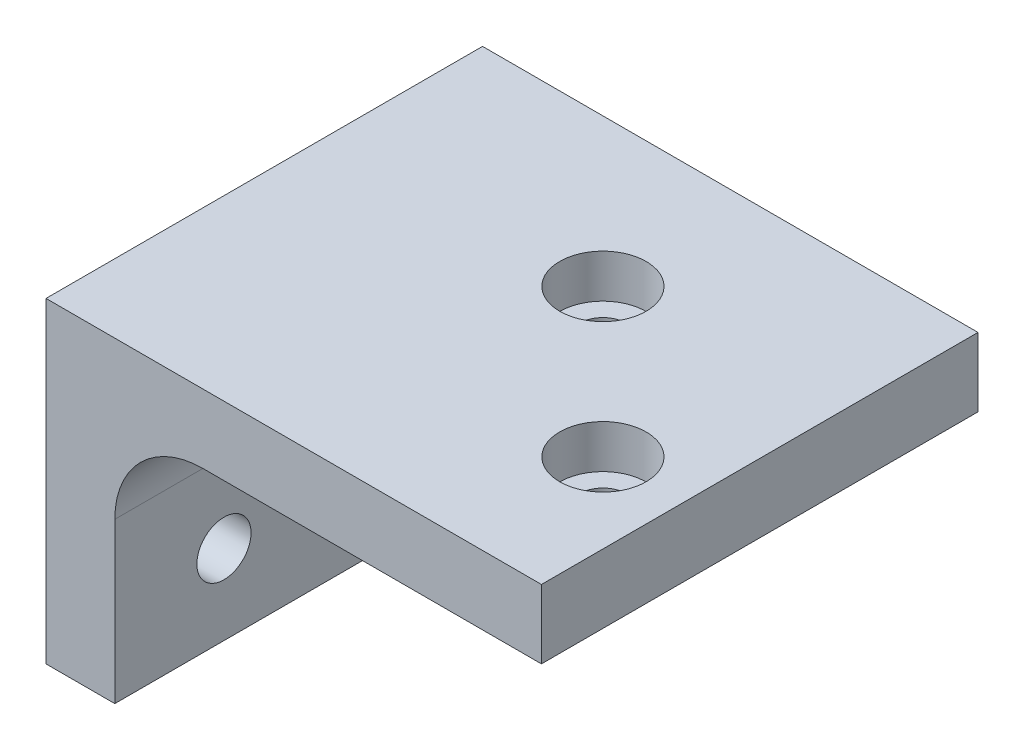
SolidWorks part; units mm, degrees
ref_plane "Front Plane" through (0, 0, 0) normal (0, 0, 1) x (1, 0, 0)
ref_plane "Top Plane" through (0, 0, 0) normal (0, 1, 0) x (1, 0, 0)
ref_plane "Right Plane" through (0, 0, 0) normal (1, 0, 0) x (0, 0, -1)
sketch "Sketch1" plane through (0, 0, 0) normal (0, 0, 1) x (1, 0, 0)
  line L3 (9.4, 125.8309) -> (9.4, 96.6209)
  line L10 (22.8594, 119.4809) -> (55.12, 119.4809)
  line L11 (55.12, 119.4809) -> (55.12, 125.8309)
  line L12 (55.12, 125.8309) -> (9.4, 125.8309)
  line L13 (9.4, 96.6209) -> (15.75, 96.6209)
  line L14 (15.75, 96.6209) -> (15.75, 111.3529)
  line L15 (23.878, 119.4809) -> (22.8594, 119.4809)
  arc A0 (23.878, 119.4809) -> (15.75, 111.3529) centre (23.878, 111.3529) ccw
  dimension "D4" = 8.128
  dimension "D1" = 6.35
  dimension "D2" = 6.35
  dimension "D5" = 29.21
  dimension "D6" = 45.72
extrude "Boss-Extrude1" add sketch "Sketch1" against normal blind 40.2844 contours A0 L15 L10 L11 L12 L3 L13 L14 region at (32.26, 125.2883, 0)
sketch "Sketch2" plane through (0, 119.4809, 0) normal (0, -1, 0) x (-1, 0, 0)
  line L0 (-47.7568, 13.0348) -> (-34.1337, 26.6579) construction
  line L1 (-55.12, 0) -> (-9.4, 0) construction
  line L2 (-50.5146, 6.0491) -> (-54.7425, 10.277) construction
  line L3 (-50.5146, 6.0491) -> (-27.148, 29.4157) construction
  line L4 (-54.7425, 10.277) -> (-31.3759, 33.6436) construction
  line L5 (-27.148, 29.4157) -> (-31.3759, 33.6436) construction
  line L6 (-38.8313, 17.7324) -> (-40.9453, 19.8464) construction
  line L7 (-40.9453, 19.8464) -> (-43.0592, 21.9603) construction
  line L8 (-52.4706, -10.1316) -> (-10.9673, 31.3717) construction
  line L9 (-31.719, 10.62) -> (-38.8313, 17.7324) construction
  line L12 (-55.12, 40.2844) -> (-55.12, 0) construction
  line L13 (-23.878, 40.2844) -> (-23.878, 0) construction
  circle A0 centre (-47.7568, 13.0348) radius 2.1336
  circle A1 centre (-34.1337, 26.6579) radius 2.1336
  dimension "D2" = 4.2672
  dimension "D3" = 4.2672
  dimension "D1" = 45
  dimension "D4" = 5.9792
  dimension "D5" = 33.0454
  dimension "D6" = 19.2659
  dimension "D7" = 10.0584
  dimension "D8" = 3.27
  dimension "D9" = 13.0348
extrude "Cut-Extrude1" cut sketch "Sketch2" against normal through all
sketch "Sketch3" plane through (0, 125.8309, 0) normal (0, 1, 0) x (1, 0, 0)
  circle A0 centre (47.7568, 13.0348) radius 3.9878
  circle A1 centre (34.1337, 26.6579) radius 3.9878
  dimension "D1" = 7.9756
  dimension "D2" = 7.9756
extrude "Cut-Extrude2" cut sketch "Sketch3" against normal blind 4
sketch "Sketch4" plane through (15.75, 0, 0) normal (1, 0, 0) x (0, 0, -1)
  line L0 (0, 96.6209) -> (0, 111.3529) construction
  line L1 (0, 103.9869) -> (10.0711, 103.9869) construction
  line L2 (10.0711, 103.9869) -> (20.1422, 103.9869) construction
  line L3 (20.1422, 103.9869) -> (30.2133, 103.9869) construction
  line L4 (30.2133, 103.9869) -> (40.2844, 103.9869) construction
  line L5 (40.2844, 96.6209) -> (40.2844, 111.3529) construction
  circle A0 centre (10.0711, 103.9869) radius 2.5
  circle A1 centre (30.2133, 103.9869) radius 2.5
  point P7 (0, 103.9869)
  dimension "D1" = 5
  dimension "D2" = 5
extrude "Cut-Extrude3" cut sketch "Sketch4" against normal through all
